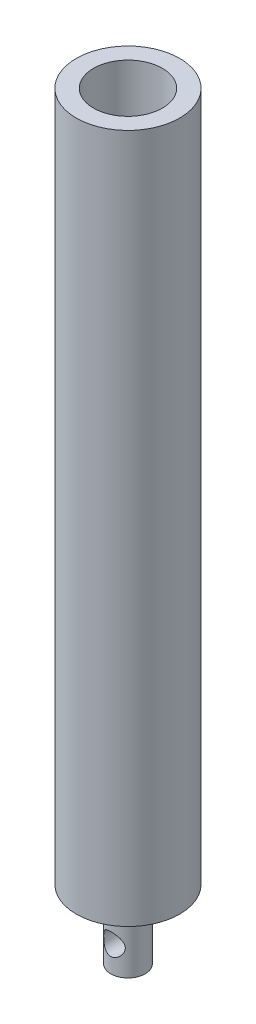
SolidWorks part; units mm, degrees
material "Plain Carbon Steel"
ref_plane "Front Plane" through (0, 0, 0) normal (0, 0, 1) x (1, 0, 0)
ref_plane "Top Plane" through (0, 0, 0) normal (0, 1, 0) x (1, 0, 0)
ref_plane "Right Plane" through (0, 0, 0) normal (1, 0, 0) x (0, 0, -1)
sketch "Sketch1" plane through (0, 0, 0) normal (0, 1, 0) x (1, 0, 0)
  circle A0 centre (0, 0) radius 6.35
  circle A1 centre (0, 0) radius 19.05
  dimension "D1" = 12.7
  dimension "D2" = 38.1
extrude "Boss-Extrude1" add sketch "Sketch1" along normal blind 254 contours A0 | A1 A0 region at (0, 0, 0) region at (-18.5112, 0, 0)
extrude "Boss-Extrude2" add sketch "Sketch1<3>" against normal blind 25.4 contours A0 region at (0, 0, 0)
sketch "Sketch1<3>" plane through (0, 0, 0) normal (0, 1, 0) x (1, 0, 0) same geometry as "Sketch1"
sketch "Sketch2" plane through (0, 254, 0) normal (0, 1, 0) x (1, 0, 0)
  circle A0 centre (0, 0) radius 12.7
  dimension "D1" = 25.4
extrude "Cut-Extrude1" cut sketch "Sketch2" against normal blind 203.2
sketch "Sketch3" plane through (0, 0, 0) normal (0, 0, 1) x (1, 0, 0)
  line L0 (-6.35, -25.4) -> (6.35, -25.4) construction
  circle A0 centre (0, -15.875) radius 3.9688
  dimension "D1" = 7.9375
  dimension "D2" = 9.525
extrude "Cut-Extrude2" cut sketch "Sketch3" against normal through all both and the other way through all
